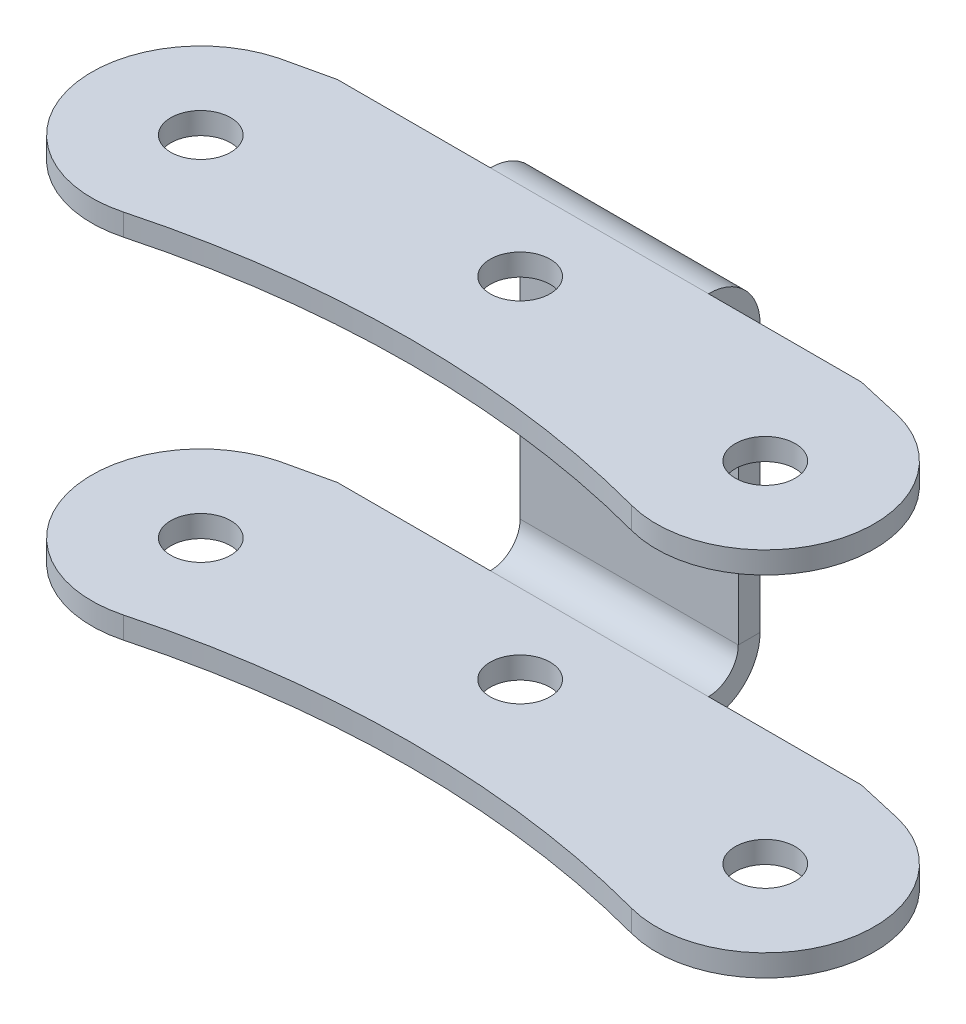
SolidWorks part; units mm, degrees
note: The reader was unsure of these and kept them because the rebuilt part matched: flange length of "边线-法兰1".
ref_plane "前视基准面" through (0, 0, 0) normal (0, 0, 1) x (1, 0, 0)
ref_plane "上视基准面" through (0, 0, 0) normal (0, 1, 0) x (1, 0, 0)
ref_plane "右视基准面" through (0, 0, 0) normal (1, 0, 0) x (0, 0, -1)
sketch "草图1" plane through (0, 0, 0) normal (0, 0, 1) x (1, 0, 0)
  line L0 (0, 0) -> (0, 17.7803) construction
  line L1 (-10, 17) -> (10, 17)
  line L2 (-10, 17) -> (-10, -17)
  line L3 (-10, -17) -> (10, -17)
  line L4 (10, 17) -> (10, -17)
  line L5 (-10, 17) -> (10, -17) construction
  line L6 (-10, -17) -> (10, 17) construction
  line L7 (0, 0) -> (28.0759, 0) construction
  point P0 (0, 0)
  dimension "D1" = 20
  dimension "D2" = 34
base flange "基体-法兰1" sketch "草图1" thickness 2 reverse thickness direction no parameters "D1"=2.7366
edge flange "边线-法兰1" sketch "草图8" flange angle 90 flange length 25.0667 flange position material inside bend radius 2.7366 thickness 2 relief rectangular parameters "D6"=10
sketch "草图8" plane through (0, 17, 0) normal (0, -1, 0) x (1, 0, 0)
  line L7 (12, 0) -> (-12, 0)
  line L8 (10, 0) -> (-10, 0) construction
  line L9 (-10, -2) -> (-10, 0) construction
  line L10 (0, 110) -> (0, 10) construction
  line L11 (0, 110) -> (25.8819, 13.4074) construction
  line L12 (-25.8819, 13.4074) -> (0, 110) construction
  line L15 (-12, 0) -> (-28.4701, 3.7482)
  line L16 (12, 0) -> (28.4701, 3.7482)
  arc A1 (-23.2937, 23.0667) -> (23.2937, 23.0667) centre (0, 110) ccw
  arc A2 (-35.3997, 16.4753) -> (35.3997, 16.4753) centre (0, 110) ccw construction
  arc A6 (-23.2937, 23.0667) -> (-28.4701, 3.7482) centre (-25.8819, 13.4074) ccw
  arc A7 (28.4701, 3.7482) -> (23.2937, 23.0667) centre (25.8819, 13.4074) ccw
  point P11 (0, 0)
  point P14 (-10, -1)
  dimension "D8" = 180
  dimension "D9" = 200
  dimension "D1" = 24
  dimension "D2" = 10
  dimension "D3" = 16.4701
  dimension "D4" = 16.4701
  dimension "D10" = 110
  dimension "D13" = 15
  dimension "D14" = 15
bend "边线折弯1" bend radius 2.7366 bend angle 90 parameters "D5"=1
mirror "镜向1" about plane through (0, 0, 0) normal (0, 1, 0) of "边线-法兰1"
bend "镜向折弯1" bend radius 2.7366 bend angle 90 parameters "D5"=2
sketch "草图9" plane through (0, 17, 0) normal (0, 1, 0) x (1, 0, 0)
  line L0 (0, -110) -> (25.8819, -13.4074) construction
  line L1 (0, -10) -> (0, -110) construction
  circle A0 centre (0, -110) radius 100 construction
  circle A1 centre (0, -10) radius 2.75
  circle A2 centre (25.8819, -13.4074) radius 2.75
  circle A3 centre (-25.8819, -13.4074) radius 2.75
  dimension "D2" = 200
  dimension "D4" = 5.5
  dimension "D1" = 110
  dimension "D3" = 15
extrude "切除-拉伸1" cut sketch "草图9" against normal through all normal cut yes
sketch "折弯-线1" plane through (0, 0, 0) normal (0, 1, 0) x (1, 0, 0)
sketch "边界框1" plane through (0, 0, 0) normal (0, 1, 0) x (1, 0, 0)
sheet metal parameters "钣金6" thickness 2 parameters "D1"=2.7366
flat pattern "平板型式6" [suppressed]
sketch "折弯-线2" plane through (0, 0, 0) normal (0, 1, 0) x (1, 0, 0)
sketch "边界框2" [suppressed] plane through (0, 0, 0) normal (0, 1, 0) x (1, 0, 0)
sheet metal parameters "钣金7" thickness 2 parameters "D1"=2.7366
flat pattern "平板型式6" [suppressed]
sketch "折弯-线2" plane through (0, 0, 0) normal (0, 1, 0) x (1, 0, 0)
sketch "边界框2" [suppressed] plane through (0, 0, 0) normal (0, 1, 0) x (1, 0, 0)
bend of the flat pattern "展开-<边线折弯1>1"
sheet metal parameters "钣金8" thickness 2 parameters "D1"=2.7366
flat pattern "平板型式6" [suppressed]
sketch "折弯-线2" plane through (0, 0, 0) normal (0, 1, 0) x (1, 0, 0)
sketch "边界框2" [suppressed] plane through (0, 0, 0) normal (0, 1, 0) x (1, 0, 0)
bend of the flat pattern "展开-<边线折弯1>1"
bend of the flat pattern "展开-<镜向折弯1>1"
sheet metal parameters "钣金9" thickness 2 parameters "D1"=2.7366
flat pattern "平板型式6" [suppressed]
sketch "折弯-线2" plane through (0, 0, 0) normal (0, 1, 0) x (1, 0, 0)
sketch "边界框2" [suppressed] plane through (0, 0, 0) normal (0, 1, 0) x (1, 0, 0)
bend of the flat pattern "展开-<边线折弯1>1"
bend of the flat pattern "展开-<镜向折弯1>1"
